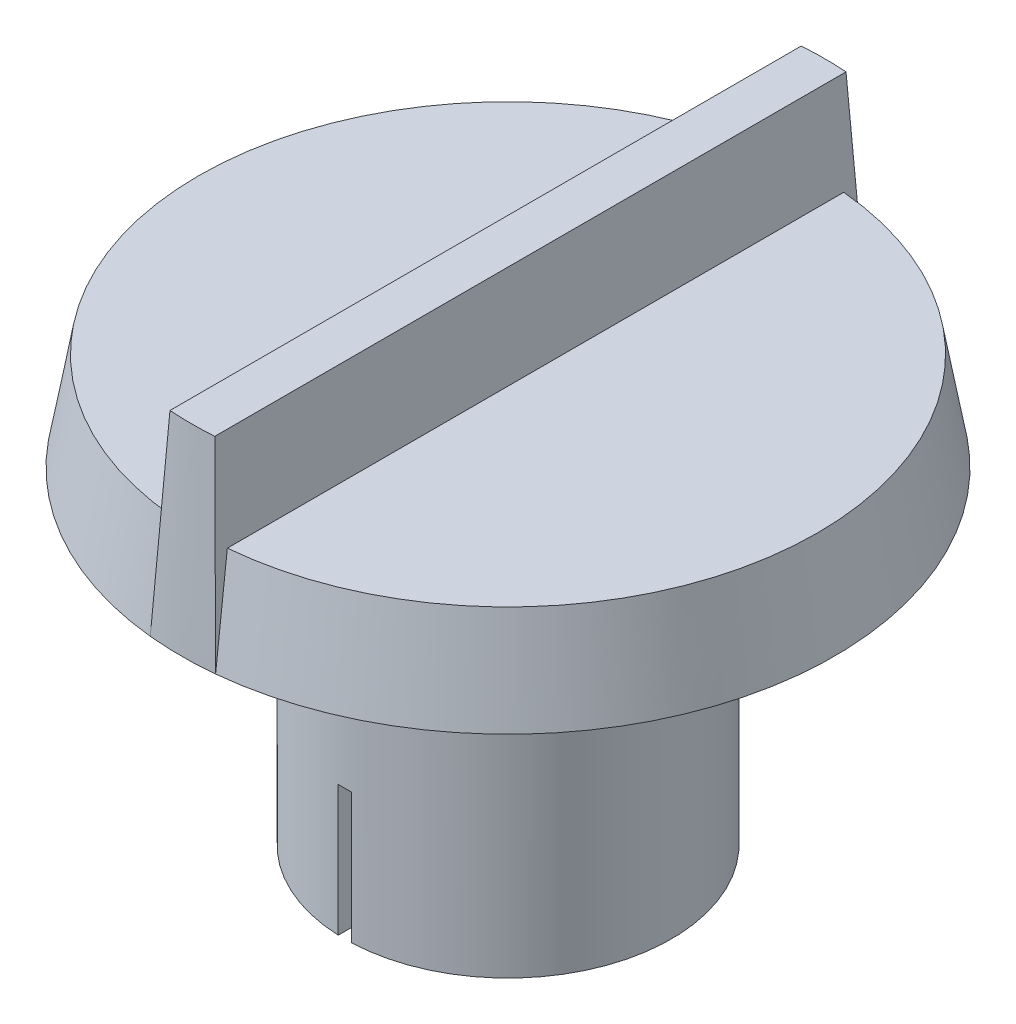
SolidWorks part; units mm, degrees
ref_plane "Plano frontal" through (0, 0, 0) normal (0, 0, 1) x (1, 0, 0)
ref_plane "Plano superior" through (0, 0, 0) normal (0, 1, 0) x (1, 0, 0)
ref_plane "Plano direito" through (0, 0, 0) normal (1, 0, 0) x (0, 0, -1)
sketch "Esboço1" plane through (0, 0, 0) normal (0, 1, 0) x (1, 0, 0)
  line L0 (0, 0) -> (0, 3)
  line L1 (0, 3) -> (0, -3)
  line L2 (-1, 9.9499) -> (-1, -10)
  line L3 (1, 9.9499) -> (1, -10)
  line L4 (-0.2, 2.9933) -> (-0.2, -2.9933)
  line L5 (-1, 10) -> (-1, -10) construction
  line L6 (1, 10) -> (1, -10) construction
  line L7 (0, 10) -> (0, -10) construction
  line L8 (0.2, 2.9933) -> (0.2, -2.9933)
  line L9 (0.2, 3) -> (0.2, -3) construction
  line L10 (-0.2, 3) -> (-0.2, -3) construction
  circle A0 centre (0, 0) radius 3
  circle A1 centre (0, 0) radius 5
  circle A2 centre (0, 0) radius 10
  dimension "D1" = 1
  dimension "D2" = 1
  dimension "D3" = 0.2
  dimension "D4" = 0.2
sketch "Esboço2" plane through (0, 0, 0) normal (0, 1, 0) x (1, 0, 0)
  line L0 (-1, -10) -> (-1, 9.9499)
  line L2 (1, 9.9499) -> (1, -10)
  circle A0 centre (0, 0) radius 10
extrude "Ressalto-extrusão1" add sketch "Esboço2" along normal blind 3 draft 10 contours L0 A0 | L2 A0 L0 | L2 A0 region at (-4.7894, 0, 0) region at (0, 0, 0) region at (4.7894, 0, 0)
extrude "Ressalto-extrusão2" add sketch "Esboço2<3>" along normal blind 6 draft 3 contours L2 A0 L0 region at (0, 0, 0)
sketch "Esboço2<3>" plane through (0, 0, 0) normal (0, 1, 0) x (1, 0, 0) same geometry as "Esboço2"
sketch "Esboço3" plane through (0, 0, 0) normal (0, 1, 0) x (1, 0, 0)
  line L0 (-0.2, 4.996) -> (-0.2, 2.9933)
  line L1 (-0.2, -2.9933) -> (0.2, -2.9933)
  line L2 (0.2, -4.996) -> (0.2, -2.9933)
  line L3 (-0.2, -2.9933) -> (-0.2, -4.996)
  line L4 (0.2, 2.9933) -> (0.2, 4.996)
  circle A0 centre (0, 0) radius 5
  circle A1 centre (0, 0) radius 3
extrude "Ressalto-extrusão3" add sketch "Esboço3" against normal blind 6 contours A1 L0 A0 L3 | A1 L2 A0 L4 | A1 L4 A0 L0 | A1 L3 A0 L2 region at (0, 0, -3.9982) region at (-0.3109, 0, -3.9947) region at (3.5256, 0, -3.3873) region at (0, 0, 3.9982)
extrude "Ressalto-extrusão4" add sketch "Esboço3<3>" against normal blind 10 contours A1 L2 A0 L4 | A1 L0 A0 L3 region at (-0.3109, 0, -3.9947) region at (3.5256, 0, -3.3873)
sketch "Esboço3<3>" plane through (0, 0, 0) normal (0, 1, 0) x (1, 0, 0) same geometry as "Esboço3"
